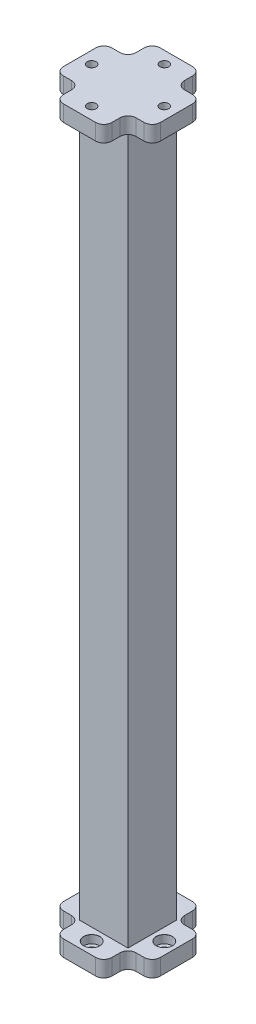
SolidWorks part; units mm, degrees
ref_plane "Front Plane" through (0, 0, 0) normal (0, 0, 1) x (1, 0, 0)
ref_plane "Top Plane" through (0, 0, 0) normal (0, 1, 0) x (1, 0, 0)
ref_plane "Right Plane" through (0, 0, 0) normal (1, 0, 0) x (0, 0, -1)
sketch "Sketch1" plane through (0, 0, 0) normal (0, 1, 0) x (1, 0, 0)
  line L1 (-15, -15) -> (15, -15)
  line L2 (-15, -15) -> (-15, 15)
  line L3 (-15, 15) -> (15, 15)
  line L4 (15, -15) -> (15, 15)
  line L5 (-15, -15) -> (15, 15) construction
  line L6 (-15, 15) -> (15, -15) construction
  point P0 (0, 0)
  dimension "D1" = 30
  dimension "D2" = 30
extrude "Boss-Extrude1" add sketch "Sketch1" along normal blind 458
sketch "Sketch2" plane through (0, 0, 0) normal (0, 1, 0) x (1, 0, 0)
  line L0 (-15, -15) -> (-30, -15)
  line L1 (-30, -15) -> (-30, 15)
  line L2 (-30, 15) -> (-15, 15)
  line L3 (15, 15) -> (-15, 15) construction
  line L4 (-15, 15) -> (-15, -15) construction
  line L5 (-15, 15) -> (-15, -15)
  line L6 (-15, 15) -> (15, 15)
  line L7 (15, 15) -> (15, 30)
  line L8 (15, 30) -> (-15, 30)
  line L9 (-15, 30) -> (-15, 15)
  line L10 (-15, -15) -> (15, -15)
  line L11 (15, -15) -> (15, -30)
  line L12 (15, -30) -> (-15, -30)
  line L13 (-15, -30) -> (-15, -15)
  line L14 (15, 15) -> (15, -15)
  line L15 (15, 15) -> (30, 15)
  line L16 (30, 15) -> (30, -15)
  line L17 (30, -15) -> (15, -15)
  dimension "D1" = 15
extrude "Boss-Extrude2" add sketch "Sketch2" along normal blind 10 contours L17 L16 L15 L14 | L13 L12 L11 L10 | L8 L9 L6 L7 | L5 L2 L1 L0 region at (-22.5, 0, 0) region at (0, 0, 22.5) region at (0, 0, -22.5) region at (22.5, 0, 0)
sketch "Sketch5" plane through (0, 10, 0) normal (0, 1, 0) x (1, 0, 0)
  line L0 (-15, -30) -> (-15, -15) construction
  line L1 (-30, 15) -> (-15, 15) construction
  line L2 (-15, 30) -> (-15, 15) construction
  line L3 (15, 15) -> (30, 15) construction
  point P0 (-22.5, 0)
  point P2 (22.5, 0)
  point P4 (0, 22.5)
  point P6 (0, -22.5)
  point P11 (-15, -22.5)
  point P19 (-22.5, 15)
  point P22 (-15, 22.5)
  point P25 (22.5, 15)
hole_wizard "CBORE for M5 SHCS1" positions "Sketch5" profile "Sketch4" counterbore size "M5" standard "ANSI Metric" end condition through all
sketch "Sketch4" plane through (-22.5, 10, 0) normal (1, 0, 0) x (0, 0, 1)
  line L0 (0, 0) -> (0, 10)
  line L1 (0, 10) -> (2.75, 10)
  line L3 (2.75, 10) -> (2.75, 5)
  line L4 (5, 5) -> (2.75, 5)
  line L5 (5, 5) -> (5, 0.025)
  line L6 (5, 0.025) -> (5.025, 0)
  line L7 (5.025, 0) -> (0, 0)
  line L8 (-5, 0.025) -> (-5.025, 0) construction
  line L11 (0, -6.35) -> (0, 107.95) construction
  dimension "Thru Hole Dia." = 5.5
  dimension "Thru Hole Depth" = 10
  dimension "C'Bore Dia." = 10
  dimension "C'Bore Depth" = 5
  dimension "Near C'Sink Dia." = 10.05
  dimension "Near C'Sink Angle" = 90
fillet "Fillet1" radius 5 12 edges at (-15, 5, 30) (15, 5, 30) (15, 5, 15) (30, 5, 15) (30, 5, -15) (15, 5, -30) (15, 5, -15) (-15, 5, -30) (-30, 5, -15) (-15, 5, -15) (-30, 5, 15) (-15, 5, 15)
ref_plane "Plane1" through (0, 229, 0) normal (0, 1, 0) x (1, 0, 0)
mirror "Mirror1" about plane through (0, 229, 0) normal (0, 1, 0) of "CBORE for M5 SHCS1", "Fillet1", "Boss-Extrude2"
